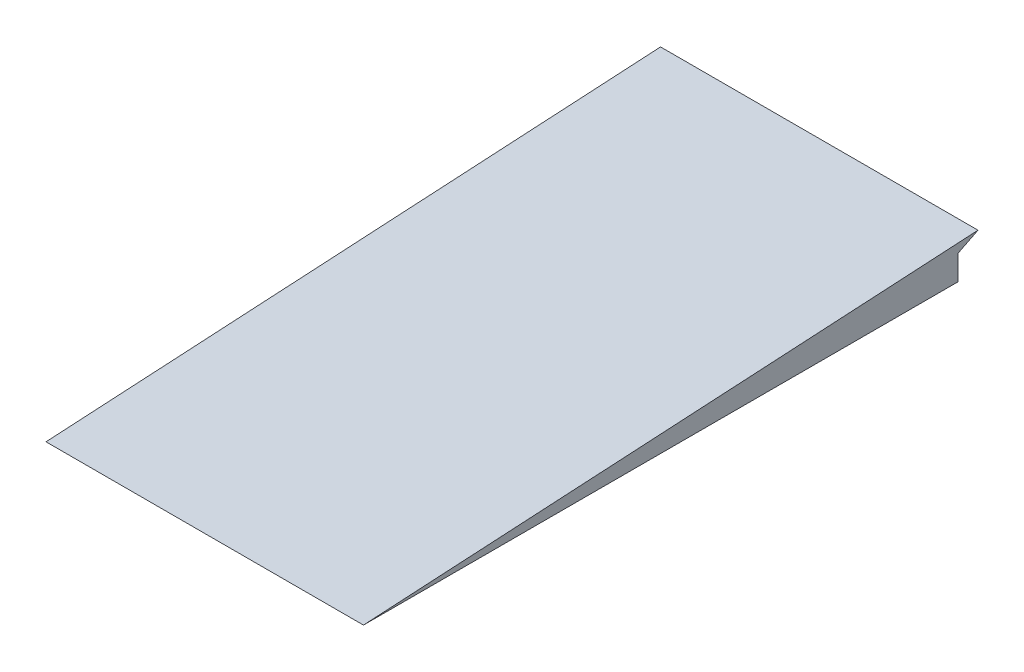
SolidWorks part; units mm, degrees
material "Pine"
ref_plane "Front" through (0, 0, 0) normal (0, 0, 1) x (1, 0, 0)
ref_plane "Top" through (0, 0, 0) normal (0, 1, 0) x (1, 0, 0)
ref_plane "Right" through (0, 0, 0) normal (1, 0, 0) x (0, 0, -1)
sketch "Sketch1" plane through (0, 0, 0) normal (1, 0, 0) x (0, 0, -1)
  line L0 (0, 0) -> (3045.353, 127)
  line L1 (3045.353, 127) -> (3045.353, 0)
  line L2 (3045.353, 0) -> (0, 0)
  dimension "D1" = 127
  dimension "D2" = 3048
extrude "Boss-Extrude1" add sketch "Sketch1" along normal mid plane 1625.6
sketch "Sketch2" plane through (812.8, 0, 0) normal (1, 0, 0) x (0, 0, -1)
  line L0 (3045.353, 127) -> (3146.953, 177.8)
  line L1 (3146.953, 177.8) -> (0, 0)
  line L2 (3045.353, 127) -> (0, 0)
  dimension "D1" = 101.6
  dimension "D2" = 50.8
extrude "Boss-Extrude2" add sketch "Sketch2" against normal up to surface (1625.6 mm away) up to face at (-812.8, 42.3333, -2030.2353)
